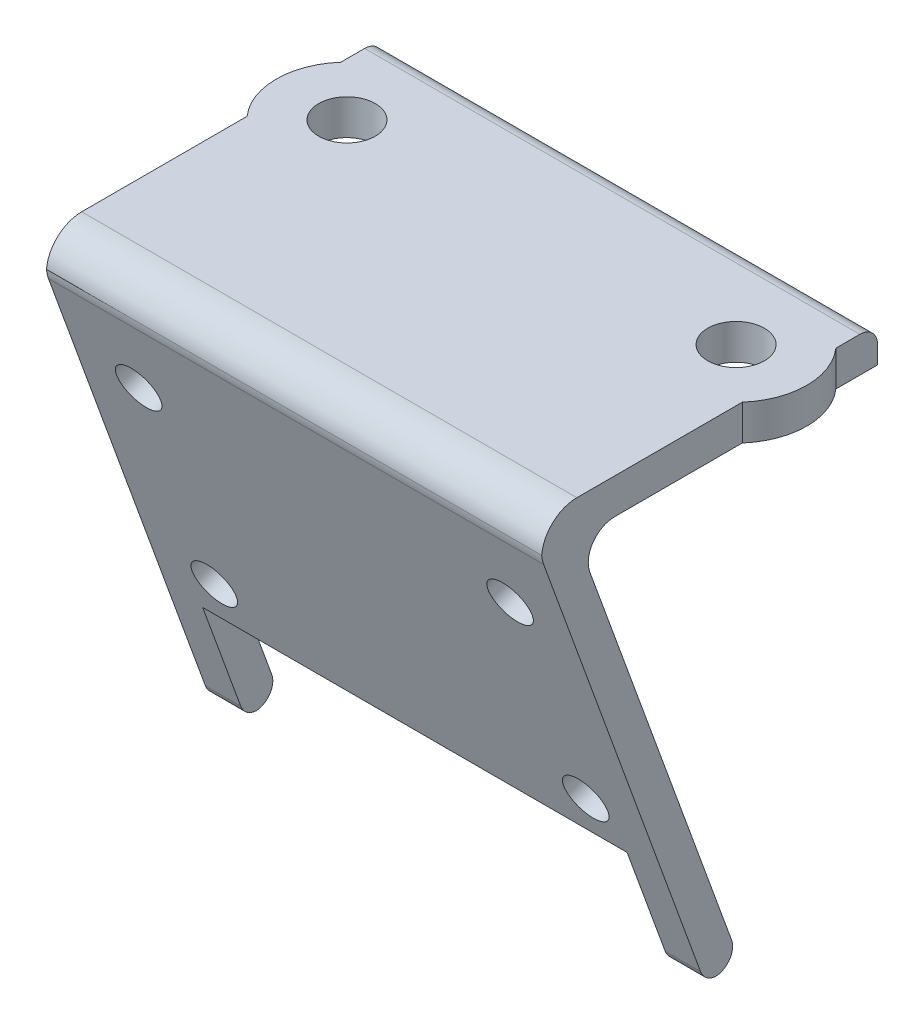
SolidWorks part; units mm, degrees
ref_plane "Płaszczyzna przednia" through (0, 0, 0) normal (0, 0, 1) x (1, 0, 0)
ref_plane "Płaszczyzna górna" through (0, 0, 0) normal (0, 1, 0) x (1, 0, 0)
ref_plane "Płaszczyzna prawa" through (0, 0, 0) normal (1, 0, 0) x (0, 0, -1)
sketch "Szkic1" plane through (0, 0, 0) normal (0, 1, 0) x (1, 0, 0)
  line L1 (-14, -9.5) -> (14, -9.5)
  line L2 (-14, -9.5) -> (-14, 9.5)
  line L3 (-14, 9.5) -> (14, 9.5)
  line L4 (14, -9.5) -> (14, 9.5)
  line L5 (-14, -9.5) -> (14, 9.5) construction
  line L6 (-14, 9.5) -> (14, -9.5) construction
  point P0 (0, 0)
  dimension "D1" = 19
  dimension "D2" = 28
extrude "Dodanie-wyciągnięcie1" add sketch "Szkic1" along normal blind 2
sketch "Szkic2" plane through (0, 2, 0) normal (0, 1, 0) x (1, 0, 0)
  line L0 (0, 0) -> (0, 4.5) construction
  line L1 (-11, 4.5) -> (11, 4.5) construction
  line L2 (14, 9.5) -> (-14, 9.5) construction
  circle A0 centre (11, 4.5) radius 1.6
  circle A1 centre (-11, 4.5) radius 1.6
  point P6 (0, 4.5)
  dimension "D2" = 3.2
  dimension "D1" = 22
  dimension "D3" = 5
extrude "Wytnij-wyciągnięcie1" cut sketch "Szkic2" against normal through all
sketch "Szkic7" plane through (0, 2, 0) normal (0, 1, 0) x (1, 0, 0)
  circle A1 centre (11, 4.5) radius 4
  circle A2 centre (11, 4.5) radius 1.6
  dimension "D1" = 8
extrude "Dodanie-wyciągnięcie3" add sketch "Szkic7" against normal up to surface (2 mm away) up to face at (11, 0, -2.9)
mirror "Lustro1" about plane through (0, 0, 0) normal (1, 0, 0) of "Dodanie-wyciągnięcie3"
sketch "Szkic3" plane through (14, 0, 0) normal (1, 0, 0) x (0, 0, -1)
  line L0 (-9.5, 2) -> (-9.5, 0) construction
  line L1 (-9.5, 0) -> (-0.2655, -25.3717)
  line L2 (-0.2655, -25.3717) -> (1.7345, -25.3717)
  line L3 (1.7345, -25.3717) -> (-7.5, 0)
  line L4 (-9.5, 0) -> (1.8542, 0) construction
  line L5 (-7.5, 0) -> (-9.5, 0)
  point P4 (-13, 0)
  point P10 (-13, 0)
  dimension "D1" = 20
  dimension "D2" = 2
  dimension "D3" = 2
  dimension "D4" = 27
extrude "Dodanie-wyciągnięcie2" add sketch "Szkic3" against normal up to surface (28 mm away) up to face at (-14, 1, -8.3229)
sketch "Szkic4" plane through (0, -3.0532, 8.3887) normal (0, -0.342, 0.9397) x (1, 0, 0)
  line L0 (0, 3.2492) -> (0, -1.7875) construction
  line L1 (-14, 3.2492) -> (14, 3.2492) construction
  line L2 (-10.5, -1.7875) -> (10.5, -1.7875) construction
  line L3 (-10.5, -1.7875) -> (-10.5, -14.2875) construction
  circle A0 centre (-10.5, -1.7875) radius 1.25
  circle A1 centre (-10.5, -14.2875) radius 1.25
  circle A2 centre (10.5, -14.2875) radius 1.25
  circle A3 centre (10.5, -1.7875) radius 1.25
  point P8 (0, -1.7875)
  dimension "D2" = 2.5
  dimension "D4" = 2.5
  dimension "D1" = 21
  dimension "D3" = 12.5
extrude "Wytnij-wyciągnięcie2" cut sketch "Szkic4" against normal up to surface (1.8794 mm away) up to face at (0, -12.6859, 2.8827)
sketch "Szkic6" plane through (0, -3.0532, 8.3887) normal (0, -0.342, 0.9397) x (1, 0, 0)
  line L0 (-14, -23.7508) -> (14, -23.7508) construction
  line L1 (-12, -23.7508) -> (12, -23.7508) construction
  line L2 (-12, -23.7508) -> (-12, -16.7508)
  line L3 (-12, -16.7508) -> (12, -16.7508)
  line L4 (12, -23.7508) -> (12, -16.7508)
  line L5 (-12, -23.7508) -> (12, -16.7508) construction
  line L6 (-12, -16.7508) -> (12, -23.7508) construction
  line L7 (-12, -23.7508) -> (-12, -25.9094)
  line L8 (-12, -25.9094) -> (12, -25.9094)
  line L9 (12, -25.9094) -> (12, -23.7508)
  point P4 (0, -20.2508)
  point P7 (0, -23.7508)
  point P8 (0, -23.7508)
  dimension "D1" = 24
  dimension "D2" = 7
extrude "Wytnij-wyciągnięcie4" cut sketch "Szkic6" against normal through all
fillet "Zaokrąglenie1" radius 2 2 edges at (0, 2, 9.5) (0, 0, 9.5)
fillet "Zaokrąglenie2" radius 1.5 1 edges at (0, 0, 7.5)
fillet "Zaokrąglenie3" radius 1 4 edges at (13, -25.3717, -1.7345) (-13, -25.3717, -1.7345) (-13, -25.3717, 0.2655) (13, -25.3717, 0.2655)
fillet "Zaokrąglenie4" radius 1 1 edges at (0, 2, -9.5)
